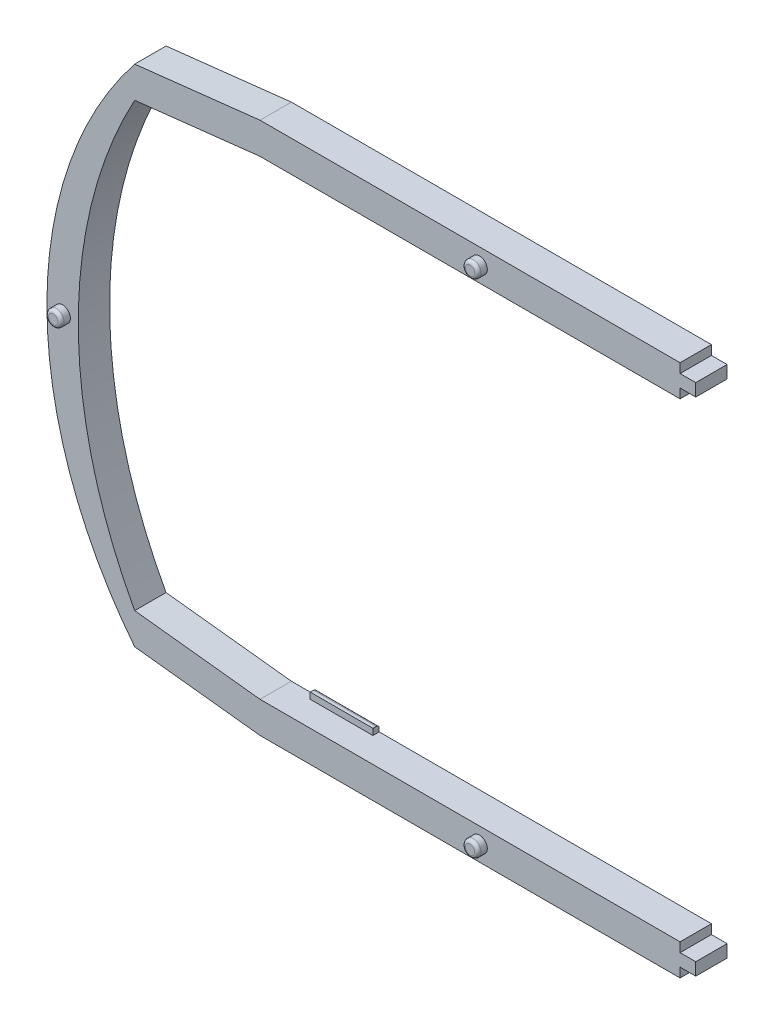
SolidWorks part; units mm, degrees
ref_plane "Plan de face" through (0, 0, 0) normal (0, 0, 1) x (1, 0, 0)
ref_plane "Plan de dessus" through (0, 0, 0) normal (0, 1, 0) x (1, 0, 0)
ref_plane "Plan de droite" through (0, 0, 0) normal (1, 0, 0) x (0, 0, -1)
sketch "Esquisse1" plane through (0, 0, 0) normal (0, 0, 1) x (1, 0, 0)
  line L0 (-166.7589, 62.5009) -> (-206.7589, 58.0009)
  line L1 (-166.7589, 62.5009) -> (-32.7589, 62.5009)
  line L2 (-166.7589, 62.5009) -> (-166.7589, -87.4991)
  line L3 (-166.7589, -87.4991) -> (-32.7589, -87.4991)
  line L5 (-166.7589, 58.0009) -> (-206.7589, 58.0009)
  line L6 (-166.7589, 58.0009) -> (-166.7589, -82.9991)
  line L7 (-166.7589, -82.9991) -> (-206.7589, -82.9991)
  line L8 (-206.7589, 58.0009) -> (-206.7589, -82.9991)
  line L9 (-166.7589, -87.4991) -> (-206.7589, -82.9991)
  line L10 (-166.7589, 72.5009) -> (-206.7589, 68.0009)
  line L11 (-166.7589, 62.5009) -> (-32.7589, 62.5009)
  line L12 (-166.7589, 62.5009) -> (-166.7589, 72.5009)
  line L13 (-166.7589, 72.5009) -> (-32.7589, 72.5009)
  line L14 (-32.7589, 62.5009) -> (-32.7589, 72.5009)
  line L15 (-166.7589, -87.4991) -> (-32.7589, -87.4991)
  line L16 (-166.7589, -87.4991) -> (-166.7589, -97.4991)
  line L17 (-166.7589, -97.4991) -> (-32.7589, -97.4991)
  line L18 (-32.7589, -87.4991) -> (-32.7589, -97.4991)
  line L19 (-166.7589, -97.4991) -> (-206.7589, -92.9991)
  line L20 (-32.7589, 69.5009) -> (-27.7589, 69.5009)
  line L21 (-32.7589, 69.5009) -> (-32.7589, 65.5009)
  line L22 (-32.7589, 65.5009) -> (-27.7589, 65.5009)
  line L23 (-27.7589, 69.5009) -> (-27.7589, 65.5009)
  line L24 (-32.7589, -90.4991) -> (-27.7589, -90.4991)
  line L25 (-32.7589, -90.4991) -> (-32.7589, -94.4991)
  line L26 (-32.7589, -94.4991) -> (-27.7589, -94.4991)
  line L27 (-27.7589, -90.4991) -> (-27.7589, -94.4991)
  line L28 (-158.7589, -87.4991) -> (-138.7589, -87.4991)
  line L29 (-158.7589, -87.4991) -> (-158.7589, -85.4991)
  line L30 (-158.7589, -85.4991) -> (-138.7589, -85.4991)
  line L31 (-138.7589, -87.4991) -> (-138.7589, -85.4991)
  line L32 (-158.7589, 62.5009) -> (-138.7589, 62.5009)
  line L33 (-158.7589, 62.5009) -> (-158.7589, 60.5009)
  line L34 (-158.7589, 60.5009) -> (-138.7589, 60.5009)
  line L35 (-138.7589, 62.5009) -> (-138.7589, 60.5009)
  arc A0 (-206.7589, 58.0009) -> (-206.7589, -82.9991) centre (-77.6964, -12.4991) ccw
  circle A1 centre (-229.7589, -12.4991) radius 2.5
  circle A2 centre (-96.7589, 67.5009) radius 2.5
  arc A3 (-206.7589, 68.0009) -> (-206.7589, -92.9991) centre (-105.0401, -12.4991) ccw
  circle A4 centre (-96.7589, -92.4991) radius 2.5
  point P9 (-206.7589, -12.4991)
  point P11 (-224.7589, -12.4991)
  point P23 (-234.7589, -12.4991)
  dimension "D22" = 20
  dimension "D1" = 134
  dimension "D2" = 150
  dimension "D3" = 141
  dimension "D4" = 4
  dimension "D5" = 5
  dimension "D6" = 40
  dimension "D7" = 18
  dimension "D8" = 3
  dimension "D9" = 10
  dimension "D10" = 10
  dimension "D11" = 5
  dimension "D12" = 10
  dimension "D13" = 10
  dimension "D14" = 10
  dimension "D15" = 3
  dimension "D16" = 4
  dimension "D17" = 70
  dimension "D18" = 70
  dimension "D19" = 5
  dimension "D20" = 5
  dimension "D21" = 5
  dimension "D23" = 2
  dimension "D24" = 48
  dimension "D25" = 20
  dimension "D26" = 2
  dimension "D27" = 48
extrude "Boss.-Extru.1" add sketch "Esquisse1" along normal blind 10 contours L1 L14 L13 L12 A2 | L10 A3 L19 L16 L9 A0 L0 L12 A1 | L18 L3 L16 L17 A4 | L23 L20 L14 L22 | L26 L27 L24 L25 region at (-99.8035, 67.5009, 0) region at (-186.9636, 62.0704, 0) region at (-99.8035, -92.4991, 0) region at (-30.2589, 67.5009, 0)
extrude "Boss.-Extru.2" add sketch "Esquisse1<3>" along normal blind 13 contours A2 | A1 | A4 region at (-229.7589, -12.4991, 0) region at (-96.7589, 67.5009, 0) region at (-96.7589, -92.4991, 0)
sketch "Esquisse1<3>" plane through (0, 0, 0) normal (0, 0, 1) x (1, 0, 0) same geometry as "Esquisse1"
fillet "Congé2" radius 1 1 edges at (-94.2589, -92.4991, 13)
fillet "Congé3" radius 1 2 edges at (-94.2589, 67.5009, 13) (-227.2589, -12.4991, 13)
extrude "Boss.-Extru.3" add sketch "Esquisse1<4>" along normal blind 2 contours L15 L31 L30 L29 | L34 L35 L32 L33 region at (-148.7589, -86.4991, 0)
sketch "Esquisse1<4>" plane through (0, 0, 0) normal (0, 0, 1) x (1, 0, 0) same geometry as "Esquisse1"
fillet "Congé4" radius 1 2 edges at (-148.7589, -85.4991, 0) (-148.7589, 60.5009, 0)
